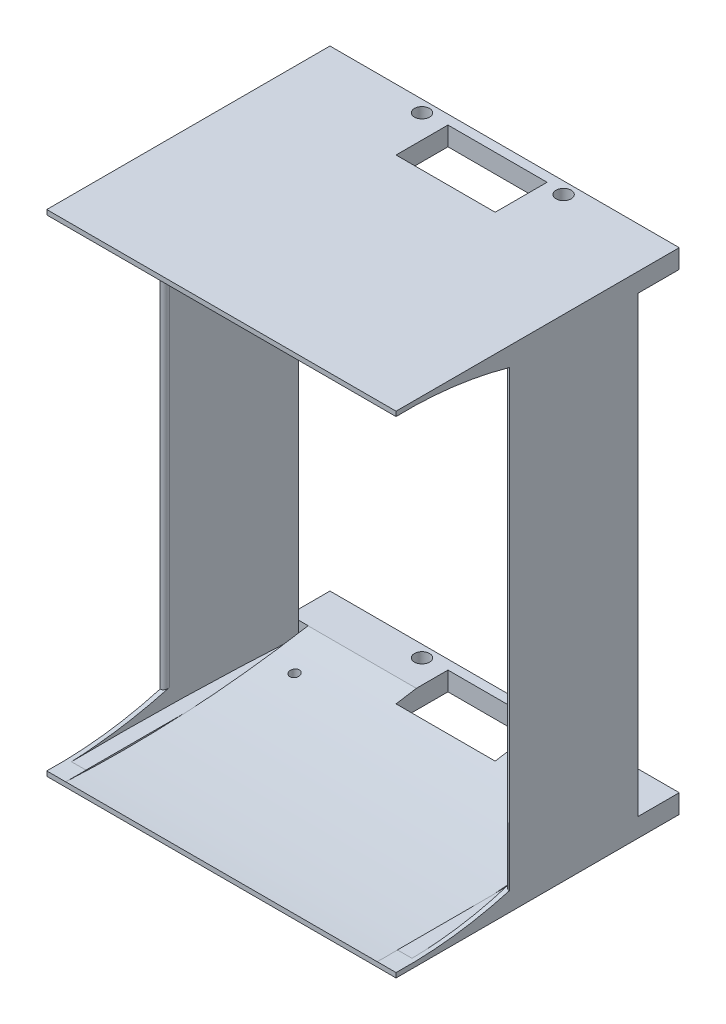
SolidWorks part; units mm, degrees
material "ABS PC"
ref_plane "Front Plane" through (0, 0, 0) normal (0, 0, 1) x (1, 0, 0)
ref_plane "Top Plane" through (0, 0, 0) normal (0, 1, 0) x (1, 0, 0)
ref_plane "Right Plane" through (0, 0, 0) normal (1, 0, 0) x (0, 0, -1)
sketch "Sketch1" plane through (0, 0, 0) normal (0, 0, 1) x (1, 0, 0)
  line L1 (37, -52) -> (-37, -52)
  line L2 (37, -52) -> (37, 52)
  line L3 (37, 52) -> (-37, 52)
  line L4 (-37, -52) -> (-37, 52)
  line L5 (37, -52) -> (-37, 52) construction
  line L6 (37, 52) -> (-37, -52) construction
  point P0 (0, 0)
  dimension "D1" = 74
  dimension "D2" = 104
extrude "Boss-Extrude1" add sketch "Sketch1" along normal blind 40
sketch "Sketch2" plane through (0, 0, 40) normal (0, 0, 1) x (1, 0, 0)
  line L0 (37, 52) -> (-37, 52) construction
  line L1 (33, -48) -> (-33, -48)
  line L2 (33, -48) -> (33, 48)
  line L3 (33, 48) -> (-33, 48)
  line L4 (-33, -48) -> (-33, 48)
  line L5 (33, -48) -> (-33, 48) construction
  line L6 (33, 48) -> (-33, -48) construction
  point P0 (0, 0)
  dimension "D1" = 4
  dimension "D2" = 66
extrude "Cut-Extrude1" cut sketch "Sketch2" against normal blind 40
sketch "Sketch3" plane through (0, -52, 0) normal (0, -1, 0) x (1, 0, 0)
  line L0 (-37, 2.5) -> (37, 2.5) construction
  line L1 (-37, 40) -> (-37, 0) construction
  line L2 (37, 40) -> (37, 0) construction
  line L3 (-37, 0) -> (37, 0) construction
  circle A0 centre (-15, 2.5) radius 1.6
  circle A1 centre (15, 2.5) radius 1.6
  dimension "D2" = 3.2
  dimension "D3" = 3.2
  dimension "D5" = 22
  dimension "D1" = 2.5
  dimension "D4" = 22
extrude "Cut-Extrude2" cut sketch "Sketch3" against normal through all
sketch "Sketch4" plane through (-37, 0, 0) normal (-1, 0, 0) x (0, 0, 1)
  line L0 (0, 48) -> (8.7, 48)
  line L1 (0, 52) -> (0, -52) construction
  line L2 (8.7, 48) -> (8.7, -48)
  line L3 (8.7, -48) -> (0, -48)
  line L4 (0, -48) -> (0, 48)
  line L5 (40, -52) -> (0, -52) construction
  dimension "D1" = 4
  dimension "D2" = 4
  dimension "D3" = 8.7
extrude "Cut-Extrude3" cut sketch "Sketch4" against normal through all
sketch "Sketch5" plane through (0, -52, 0) normal (0, -1, 0) x (1, 0, 0)
  line L0 (-37, 40) -> (-37, 0) construction
  line L1 (37, 40) -> (37, 0) construction
  line L2 (-37, 0) -> (37, 0) construction
  circle A0 centre (-27, 9) radius 1
  circle A1 centre (-27, 17.5) radius 1
  circle A2 centre (27, 9) radius 1
  circle A3 centre (27, 17.5) radius 1
  dimension "D1" = 2
  dimension "D2" = 2
  dimension "D5" = 8.5
  dimension "D6" = 9
  dimension "D7" = 10
  dimension "D3" = 10
  dimension "D4" = 10
  dimension "D8" = 10
extrude "Cut-Extrude4" cut sketch "Sketch5" against normal blind 3.5
sketch "Sketch8" plane through (0, -52, 0) normal (0, -1, 0) x (1, 0, 0)
  line L0 (37, 40) -> (37, 0) construction
  line L1 (11, 2) -> (-10, 2)
  line L2 (11, 2) -> (11, 13)
  line L3 (11, 13) -> (-10, 13)
  line L4 (-10, 2) -> (-10, 13)
  line L5 (11, 2) -> (-10, 13) construction
  line L6 (11, 13) -> (-10, 2) construction
  line L7 (-37, 0) -> (37, 0) construction
  point P0 (0.5, 7.5)
  dimension "D1" = 21
  dimension "D2" = 11
  dimension "D3" = 26
  dimension "D4" = 13
sketch "Sketch9" plane through (0, 0, 40) normal (0, 0, 1) x (1, 0, 0)
  line L0 (-37, -48) -> (37, -48)
  line L1 (37, -48) -> (37, -52)
  line L2 (37, -52) -> (-37, -52)
  line L3 (-37, -52) -> (-37, -48)
  line L4 (-37, 52) -> (37, 52)
  line L5 (37, 52) -> (37, 48)
  line L6 (37, 48) -> (-37, 48)
  line L7 (-37, 48) -> (-37, 52)
extrude "Boss-Extrude2" add sketch "Sketch9" along normal blind 20
sketch "Sketch11" plane through (-33, 0, 0) normal (1, 0, 0) x (0, 0, -1)
  line L4 (-60, -48) -> (-8.7, -48)
  line L7 (-60, -48) -> (-60, -51)
  line L8 (-60, -52) -> (-60, -48) construction
  line L9 (-60, -52) -> (0, -52) construction
  line L10 (0, 0) -> (-115.729, 0) construction
  line L11 (-60, 48) -> (-60, 51)
  line L12 (-60, 48) -> (-8.7, 48)
  arc A0 (-60, -51) -> (-8.7, -48) centre (-47.547, 176.1679) ccw
  arc A1 (-60, 51) -> (-8.7, 48) centre (-47.547, -176.1679) cw
  dimension "D1" = 1
extrude "Cut-Extrude7" cut sketch "Sketch11" along normal blind 66
extrude "Cut-Extrude10" cut sketch "Sketch8" against normal through all
ref_plane "Plane1" through (0, 0, 42) normal (0, 0, 1) x (1, 0, 0)
sketch "Sketch16" plane through (0, 0, 42) normal (0, 0, 1) x (1, 0, 0)
  line L0 (-37, 48) -> (37, 48)
  line L1 (37, 48) -> (37, -48)
  line L2 (37, -48) -> (-37, -48)
  line L3 (-37, -48) -> (-37, 48)
extrude "Cut-Extrude11" cut sketch "Sketch16" against normal blind 6
sketch "Sketch18" plane through (37, 0, 0) normal (1, 0, 0) x (0, 0, -1)
  line L0 (-60, -52) -> (-60, -48) construction
  line L1 (-60, -51) -> (-60, -48)
  line L2 (-60, -48) -> (-36, -48)
  line L3 (0, 0) -> (-96.0829, 0)
  line L4 (-60, 48) -> (-36, 48)
  arc A0 (-36, -48) -> (-60, -51) centre (-57.8509, 29.3072) cw
  arc A1 (-36, 48) -> (-60, 51) centre (-57.8509, -29.3072) ccw
  line M3 (-60, 48) -> (-36, 48)
  line M14 (-60, 52) -> (-60, 48)
  dimension "D1" = 1
extrude "Cut-Extrude13" cut sketch "Sketch18" against normal through all contours A1 M3 M14 | L2 A0 L1 region at (37, 49.2513, 50.8226)
sketch "Sketch20" plane through (0, 0, 0) normal (0, 1, 0) x (1, 0, 0)
  line L0 (0, 0) -> (0, -64.621) construction
  line L1 (37, 0) -> (-37, 0) construction
  line L4 (32.9453, -59.0425) -> (32.9453, -8.668)
  line L5 (32.9453, -8.668) -> (35, -8.668)
  line L6 (32.9453, -59.0425) -> (33, -60)
  line L9 (33, -60) -> (36, -60)
  line L10 (37, -60) -> (-37, -60) construction
  line L11 (-33, -60) -> (-36, -60)
  line L12 (-32.9453, -59.0425) -> (-33, -60)
  line L13 (-32.9453, -8.668) -> (-35, -8.668)
  line L14 (-32.9453, -59.0425) -> (-32.9453, -8.668)
  line L15 (37, -60) -> (37, 0) construction
  arc A2 (35, -8.668) -> (36, -60) centre (-608.632, -46.8823) cw
  arc A3 (-35, -8.668) -> (-36, -60) centre (608.632, -46.8823) ccw
  dimension "D1" = 2
  dimension "D2" = 1
extrude "Cut-Extrude14" cut sketch "Sketch20" against normal mid plane 102 contours L11 | L5 L4 | A3 L11 L12 L14 L13 region at (34.4118, 0, 35.8066)
fillet "Fillet3" radius 1 2 edges at (36.0416, 0, 36) (-36.0416, 0, 36)
